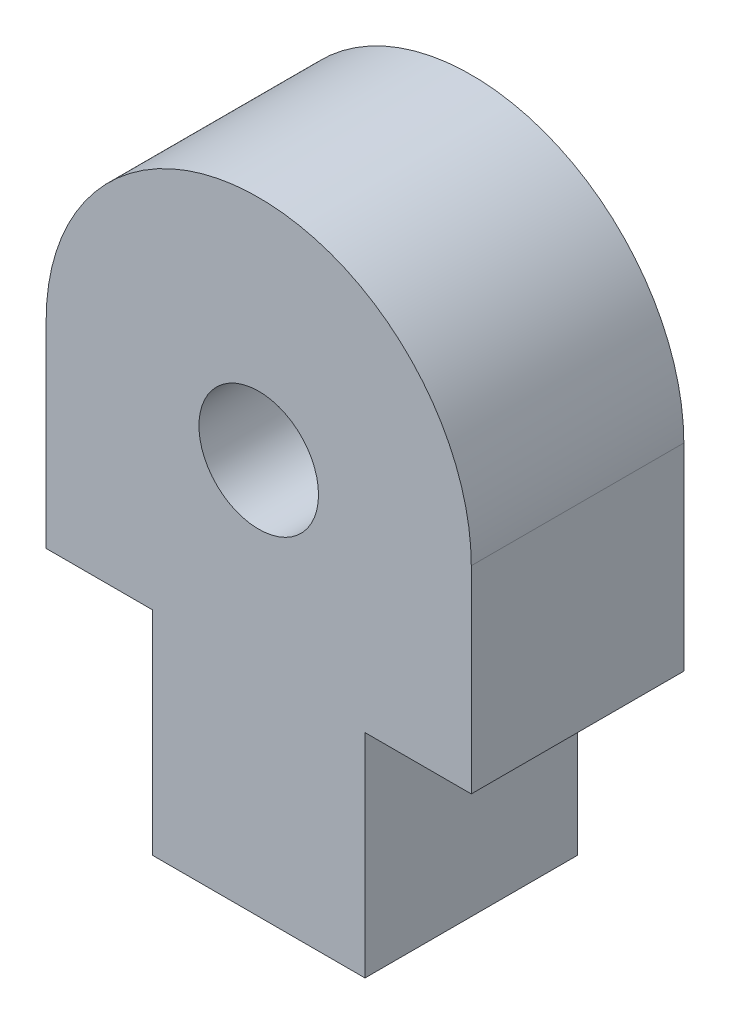
SolidWorks part; units mm, degrees
ref_plane "Front Plane" through (0, 0, 0) normal (0, 0, 1) x (1, 0, 0)
ref_plane "Top Plane" through (0, 0, 0) normal (0, 1, 0) x (1, 0, 0)
ref_plane "Right Plane" through (0, 0, 0) normal (1, 0, 0) x (0, 0, -1)
sketch "Sketch1" plane through (0, 0, 0) normal (0, 0, 1) x (1, 0, 0)
  line L0 (-6.35, 6.35) -> (-9.525, 6.35)
  line L1 (0, 0) -> (-6.35, 0)
  line L2 (0, 0) -> (0, 6.35)
  line L4 (-6.35, 0) -> (-6.35, 6.35)
  line L6 (3.175, 12.2542) -> (3.175, 6.35)
  line L7 (3.175, 6.35) -> (0, 6.35)
  line L8 (-9.525, 12.2542) -> (-9.525, 6.35)
  arc A0 (-9.525, 12.2542) -> (3.175, 12.2542) centre (-3.175, 12.2542) cw
  point P9 (-3.175, 6.35)
  dimension "D4" = 6.35
  dimension "D1" = 6.35
  dimension "D2" = 6.35
  dimension "D3" = 12.7
  dimension "D5" = 5.9042
extrude "Boss-Extrude1" add sketch "Sketch1" along normal blind 6.35
hole_wizard "9/64 (0.14063) Diameter Hole1" positions "Sketch3" profile "Sketch2" hole size "9/64" standard "ANSI Inch" end condition through all
sketch "Sketch3" plane through (0, 0, 6.35) normal (0, 0, 1) x (1, 0, 0)
  line L0 (0, 6.35) -> (3.175, 6.35) construction
  point P0 (-3.175, 11.8085)
  dimension "D1" = 5.4585
sketch "Sketch2" plane through (-3.175, 11.8085, 6.35) normal (1, 0, 0) x (0, -1, 0)
  line L0 (0, 0) -> (0, 6.35)
  line L1 (0, 6.35) -> (1.786, 6.35)
  line L2 (1.786, 6.35) -> (1.786, 0)
  line L5 (1.786, 0) -> (0, 0)
  line L11 (0, -6.35) -> (0, 107.95) construction
  dimension "Thru Hole Dia." = 3.572
  dimension "Thru Hole Depth" = 6.35
